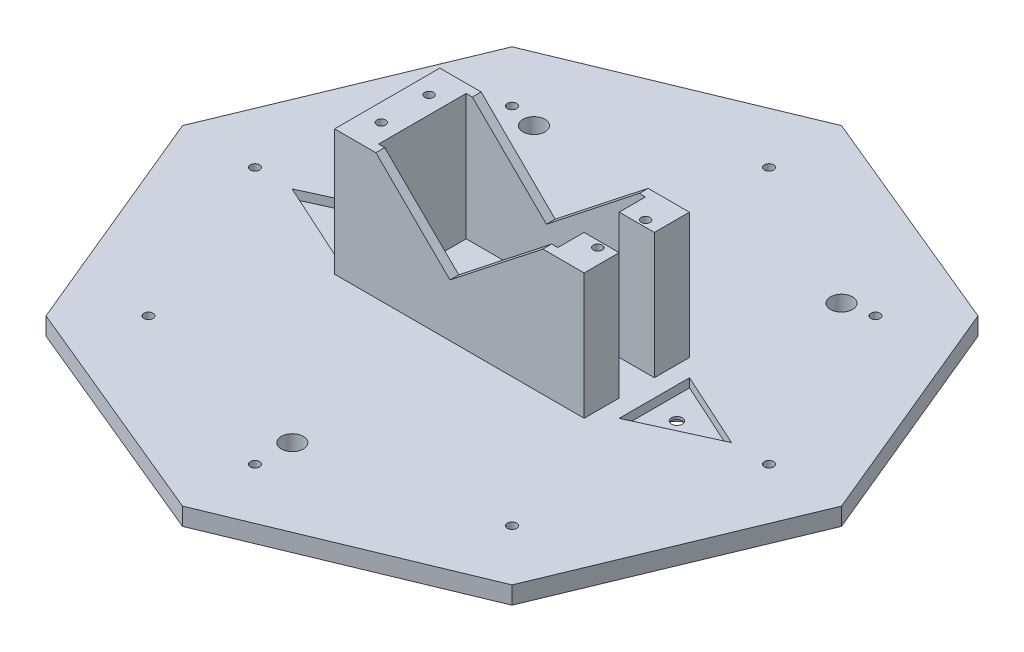
SolidWorks part; units mm, degrees
ref_plane "Ebene vorne" through (0, 0, 0) normal (0, 0, 1) x (1, 0, 0)
ref_plane "Ebene oben" through (0, 0, 0) normal (0, 1, 0) x (1, 0, 0)
ref_plane "Ebene rechts" through (0, 0, 0) normal (1, 0, 0) x (0, 0, -1)
sketch "Skizze2" plane through (0, 0, 0) normal (0, 1, 0) x (1, 0, 0)
  line L0 (-75, 0) -> (75, 0) construction
  line L1 (-55, 0) -> (55, 0) construction
  line L2 (0, -55) -> (0, 55) construction
  line L3 (-53.033, -53.033) -> (53.033, 53.033)
  line L4 (53.033, -53.033) -> (-53.033, 53.033)
  line L5 (-75, 0) -> (-53.033, 53.033)
  line L6 (-53.033, 53.033) -> (0, 75)
  line L7 (0, 75) -> (53.033, 53.033)
  line L8 (75, 0) -> (53.033, 53.033)
  line L9 (75, 0) -> (53.033, -53.033)
  line L10 (53.033, -53.033) -> (0, -75)
  line L11 (0, -75) -> (-53.033, -53.033)
  line L12 (-75, 0) -> (-53.033, -53.033)
  point P10 (0, 0)
  point P13 (0, 0)
  dimension "D1" = 150
  dimension "D2" = 75
  dimension "D3" = 150
  dimension "D4" = 150
  dimension "D5" = 45
  dimension "D6" = 45
  dimension "D7" = 75
  dimension "D8" = 75
extrude "Aufsatz-Linear austragen1" add sketch "Skizze2" along normal blind 3 and the other way blind 1 contours L7 L6 L4 L3 | L3 L0 L8 | L0 L4 L9 | L11 L10 L4 L3 | L5 L0 L4 | L0 L12 L3 region at (-42.6777, 0, -17.6777) region at (-42.6777, 0, 17.6777) region at (42.6777, 0, -17.6777) region at (0, 0, 42.6777) region at (0, 0, -42.6777) region at (42.6777, 0, 17.6777)
sketch "Skizze5" plane through (0, 0, 0) normal (0, 1, 0) x (1, 0, 0)
  line L0 (20.4, -4) -> (28.4, -4)
  line L1 (-20.4, -9.975) -> (20.4, -9.975)
  line L2 (-20.4, -9.975) -> (-20.4, 9.975)
  line L3 (-20.4, 9.975) -> (20.4, 9.975)
  line L4 (20.4, -9.975) -> (20.4, -4)
  line L5 (-20.4, -9.975) -> (20.4, 9.975) construction
  line L6 (-20.4, 9.975) -> (20.4, -9.975) construction
  line L7 (-28.4, -11.975) -> (28.4, -11.975)
  line L8 (-28.4, -11.975) -> (-28.4, 11.975)
  line L9 (-28.4, 11.975) -> (28.4, 11.975)
  line L10 (28.4, -11.975) -> (28.4, -4)
  line L11 (-28.4, -11.975) -> (28.4, 11.975) construction
  line L12 (-28.4, 11.975) -> (28.4, -11.975) construction
  line L13 (20.4, 4) -> (28.4, 4)
  line L14 (-2.2, 0) -> (2.2, 0) construction
  line L15 (20.4, 4) -> (20.4, 9.975)
  line L16 (28.4, 4) -> (28.4, 11.975)
  point P0 (0, 0)
  point P6 (0, 0)
  dimension "D1" = 40.8
  dimension "D2" = 19.95
  dimension "D3" = 2
  dimension "D4" = 8
  dimension "D5" = 4
  dimension "D6" = 4
extrude "Aufsatz-Linear austragen3" add sketch "Skizze5" along normal blind 31.65
sketch "Skizze6" plane through (0, 0, 11.975) normal (0, 0, 1) x (1, 0, 0)
  line L0 (-19, 31.65) -> (19, 31.65)
  line L1 (-28.4, 31.65) -> (28.4, 31.65) construction
  line L2 (19, 31.65) -> (-2.1527, 14.9945)
  line L3 (-2.1527, 14.9945) -> (-19, 31.65)
  line L4 (0, -2.2) -> (0, 2.2) construction
  point P5 (0, 31.65)
  dimension "D1" = 38
  dimension "D2" = 0
extrude "Schnitt-Linear austragen1" cut sketch "Skizze6" against normal blind 28.65
sketch "Skizze7" plane through (0, 3, 0) normal (0, 1, 0) x (1, 0, 0)
  line L0 (-17.9575, 0) -> (17.9575, 0) construction
  line L5 (-35, -40) -> (33.3537, 38.1186) construction
  line L6 (-33.3537, 38.1186) -> (35, -40) construction
  circle A0 centre (35, 40) radius 2.5
  circle A1 centre (-35, 40) radius 2.5
  circle A2 centre (0, -50) radius 2.5
  point P0 (0, 0)
  dimension "D3" = 5
  dimension "D4" = 5
  dimension "D5" = 5
  dimension "D6" = 50
  dimension "D1" = 80
  dimension "D2" = 70
extrude "Schnitt-Linear austragen2" cut sketch "Skizze7" against normal through all
sketch "Skizze8" plane through (0, 3, 0) normal (0, 1, 0) x (1, 0, 0)
  line L0 (-75, 0) -> (75, 0) construction
  line L7 (-32.4, 8.05) -> (-32.4, -8.05)
  line L8 (-44.1054, 2.719) -> (-32.4, -8.05) construction
  line L9 (-44.1054, -2.719) -> (-32.4, 8.05) construction
  line L12 (32.4, 8.0043) -> (32.4, -8.0043)
  line L15 (32.4, 8.0043) -> (44.0833, -2.6833) construction
  line L16 (32.4, -8.0043) -> (44.0833, 2.6833) construction
  line L17 (28.4, -11.975) -> (28.4, -4) construction
  line L18 (-28.4, 11.975) -> (-28.4, -11.975) construction
  line L19 (-50.0756, 0) -> (-32.4, -8.05)
  line L21 (-32.4, 8.05) -> (-50.0756, 0)
  line L22 (32.4, -8.0043) -> (49.9752, 0)
  line L23 (49.9752, 0) -> (32.4, 8.0043)
  line L24 (32.4, -8.0043) -> (32.4, 8.0043)
  point P2 (-41.15, 0)
  point P7 (41.15, 0)
  dimension "D1" = 4
  dimension "D2" = 4
  dimension "D3" = 16.1
extrude "Schnitt-Linear austragen6" cut sketch "Skizze8" against normal blind 2 contours L7 L21 L19 | L22 L23 L12 region at (-38.2919, 3, 0) region at (38.2584, 3, 0)
sketch "Skizze9" plane through (0, 31.65, 0) normal (0, 1, 0) x (1, 0, 0)
  circle A0 centre (-24.35, -5.425) radius 1
  circle A1 centre (-24.35, 5.475) radius 1
  circle A2 centre (24.95, 5.475) radius 1
  circle A3 centre (24.95, -5.425) radius 1
  dimension "D1" = 2
  dimension "D2" = 2
  dimension "D3" = 2
  dimension "D4" = 2
extrude "Schnitt-Linear austragen5" cut sketch "Skizze9" against normal blind 13.1
sketch "Skizze10" plane through (0, 1, 0) normal (0, 1, 0) x (1, 0, 0)
  line L1 (-0.013, 21.1078) -> (0.0217, -30.9037) construction
  line L7 (41.9977, 0.05) -> (22.7023, 0.05) construction
  line L8 (-28.4, 11.975) -> (-28.4, -11.975) construction
  line L9 (28.4, 4) -> (28.4, 11.975) construction
  circle A0 centre (-37.4878, 0) radius 1.25
  circle A1 centre (37.49, 0.05) radius 1.25
  dimension "D1" = 2.5
  dimension "D2" = 0
  dimension "D3" = 9.0878
  dimension "D4" = 9.09
extrude "Schnitt-Linear austragen7" cut sketch "Skizze10" against normal through all
sketch "Skizze11" plane through (0, -1, 0) normal (0, -1, 0) x (1, 0, 0)
  circle A0 centre (-37.4878, 0) radius 2.75
  circle A1 centre (37.49, -0.05) radius 2.75
  dimension "D1" = 5.5
  dimension "D2" = 5.5
extrude "Schnitt-Linear austragen8" cut sketch "Skizze11" against normal blind 1.4
sketch "Skizze14" plane through (0, 3, 0) normal (0, 1, 0) x (1, 0, 0)
  line L0 (0, 0) -> (-51.0988, 51.0988) construction
  line L1 (-51.0988, 51.0988) -> (0, 0) construction
  line L2 (0, 0) -> (44.6211, 44.6211) construction
  line L3 (44.6211, 44.6211) -> (0, 0) construction
  line L4 (0, 0) -> (42.9287, -42.9287) construction
  line L5 (42.9287, -42.9287) -> (0, 0) construction
  line L6 (0, 0) -> (-43.4336, -43.4336) construction
  circle A1 centre (-58.5, 0) radius 1.05
  circle A2 centre (0, 58.5) radius 1.05
  circle A3 centre (-41.3657, 41.3657) radius 1.05
  circle A4 centre (41.3657, 41.3657) radius 1.05
  circle A5 centre (58.5, 0) radius 1.05
  circle A6 centre (41.3657, -41.3657) radius 1.05
  circle A7 centre (-41.3657, -41.3657) radius 1.05
  circle A8 centre (0, -58.5) radius 1.05
  dimension "D2" = 2.1
  dimension "D3" = 2.1
  dimension "D4" = 2.1
  dimension "D5" = 2.1
  dimension "D6" = 2.1
  dimension "D7" = 2.1
  dimension "D8" = 2.1
extrude "Schnitt-Linear austragen9" cut sketch "Skizze14" against normal blind 10
